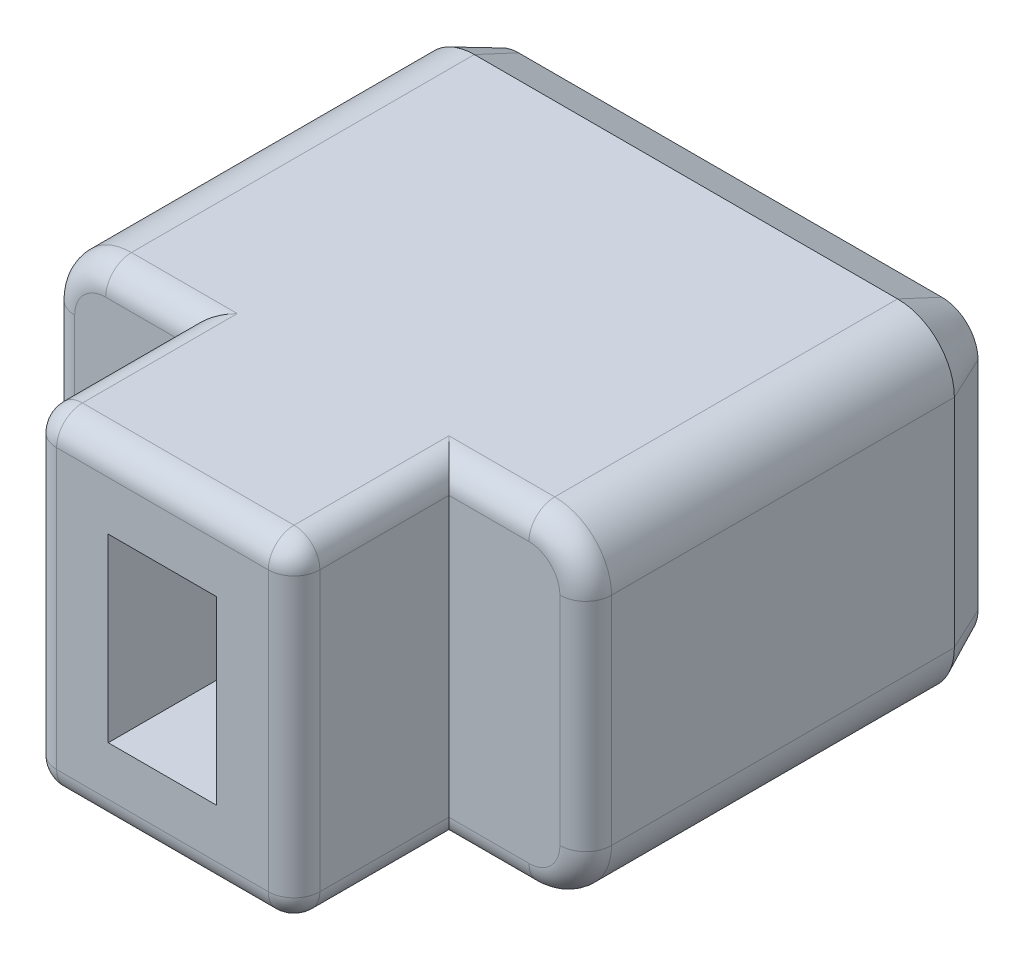
SolidWorks part; units mm, degrees
ref_plane "Plan de face" through (0, 0, 0) normal (0, 0, 1) x (1, 0, 0)
ref_plane "Plan de dessus" through (0, 0, 0) normal (0, 1, 0) x (1, 0, 0)
ref_plane "Plan de droite" through (0, 0, 0) normal (1, 0, 0) x (0, 0, -1)
sketch "Esquisse2" plane through (0, 0, 0) normal (0, 0, 1) x (1, 0, 0)
  line L1 (1.1, 0) -> (9.3, 0)
  line L2 (0, 1.1) -> (0, 5.3)
  line L3 (1.1, 6.4) -> (9.3, 6.4)
  line L4 (10.4, 1.1) -> (10.4, 5.3)
  arc A0 (9.3, 6.4) -> (10.4, 5.3) centre (9.3, 5.3) cw
  arc A1 (9.3, 0) -> (10.4, 1.1) centre (9.3, 1.1) ccw
  arc A2 (1.1, 0) -> (0, 1.1) centre (1.1, 1.1) cw
  arc A3 (0, 5.3) -> (1.1, 6.4) centre (1.1, 5.3) cw
  point P7 (10.4, 6.4)
  point P12 (0, 0)
  point P15 (0, 6.4)
  dimension "D3" = 1.1
  dimension "D1" = 10.4
  dimension "D2" = 6.4
extrude "Boss.-Extru.1" add sketch "Esquisse2" along normal blind 11
sketch "Esquisse3" plane through (0, 0, 11) normal (0, 0, 1) x (1, 0, 0)
  line L0 (0, 5.3) -> (0, 1.1) construction
  line L1 (4.15, 4.95) -> (6.25, 4.95)
  line L2 (4.15, 4.95) -> (4.15, 1.45)
  line L3 (4.15, 1.45) -> (6.25, 1.45)
  line L4 (6.25, 4.95) -> (6.25, 1.45)
  line L5 (10.4, 1.1) -> (10.4, 5.3) construction
  line L6 (9.3, 6.4) -> (1.1, 6.4) construction
  line L7 (1.1, 0) -> (9.3, 0) construction
  dimension "D1" = 2.1
  dimension "D2" = 3.5
  dimension "D3" = 4.15
  dimension "D4" = 4.15
  dimension "D5" = 1.45
  dimension "D6" = 1.45
extrude "Enlèv. mat.-Extru.1" cut sketch "Esquisse3" against normal blind 3
sketch "Esquisse4" plane through (0, 0, 11) normal (0, 0, 1) x (1, 0, 0)
  line L0 (2.65, 6.4) -> (2.65, 0)
  line L1 (9.3, 6.4) -> (1.1, 6.4) construction
  line L2 (1.1, 0) -> (9.3, 0) construction
  line L3 (2.65, 0) -> (7.75, 0)
  line L4 (7.75, 0) -> (7.75, 6.4)
  line L5 (7.75, 6.4) -> (2.65, 6.4)
  line L6 (4.15, 4.95) -> (4.15, 1.45) construction
  line L7 (6.25, 1.45) -> (6.25, 4.95) construction
  dimension "D1" = 1.5
  dimension "D2" = 1.5
extrude "Enlèv. mat.-Extru.2" cut sketch "Esquisse4" against normal blind 3 flip side to cut
fillet "Congé1" radius 0.5 18 edges at (8.525, 0, 8) (10.0778, 0.3222, 8) (10.4, 3.2, 8) (10.0778, 6.0778, 8) (1.875, 6.4, 8) (0.3222, 6.0778, 8) (1.875, 0, 8) (0.3222, 0.3222, 8) (7.75, 6.4, 9.5) (2.65, 6.4, 9.5) (7.75, 0, 9.5) (2.65, 0, 9.5) (2.65, 3.2, 11) (5.2, 6.4, 11) (7.75, 3.2, 11) (5.2, 0, 11) (8.525, 6.4, 8) (0, 3.2, 8)
chamfer "Chanfrein1" distance 0.4 angle 65 8 edges at (5.2, 0, 0) (10.0778, 0.3222, 0) (0.3222, 0.3222, 0) (10.4, 3.2, 0) (0, 3.2, 0) (10.0778, 6.0778, 0) (0.3222, 6.0778, 0) (5.2, 6.4, 0) first distance on face at (5.2, 3.2, 0)
sketch "Esquisse5" plane through (0, 0, 0) normal (0, 0, -1) x (-1, 0, 0)
  line L0 (-0.4, 5.3) -> (-10, 5.3) construction
  arc A0 (-9.3, 6) -> (-10, 5.3) centre (-9.3, 5.3) ccw construction
  text T0 "0" font "Century Gothic" height 4
extrude "Enlèv. mat.-Extru.3" cut sketch "Esquisse5" against normal blind 0.3
extrude "Boss.-Extru.2" add sketch "Esquisse5<2>" along normal blind 0.3 separate body
sketch "Esquisse5<2>" plane through (0, 0, 0) normal (0, 0, -1) x (-1, 0, 0) same geometry as "Esquisse5"
